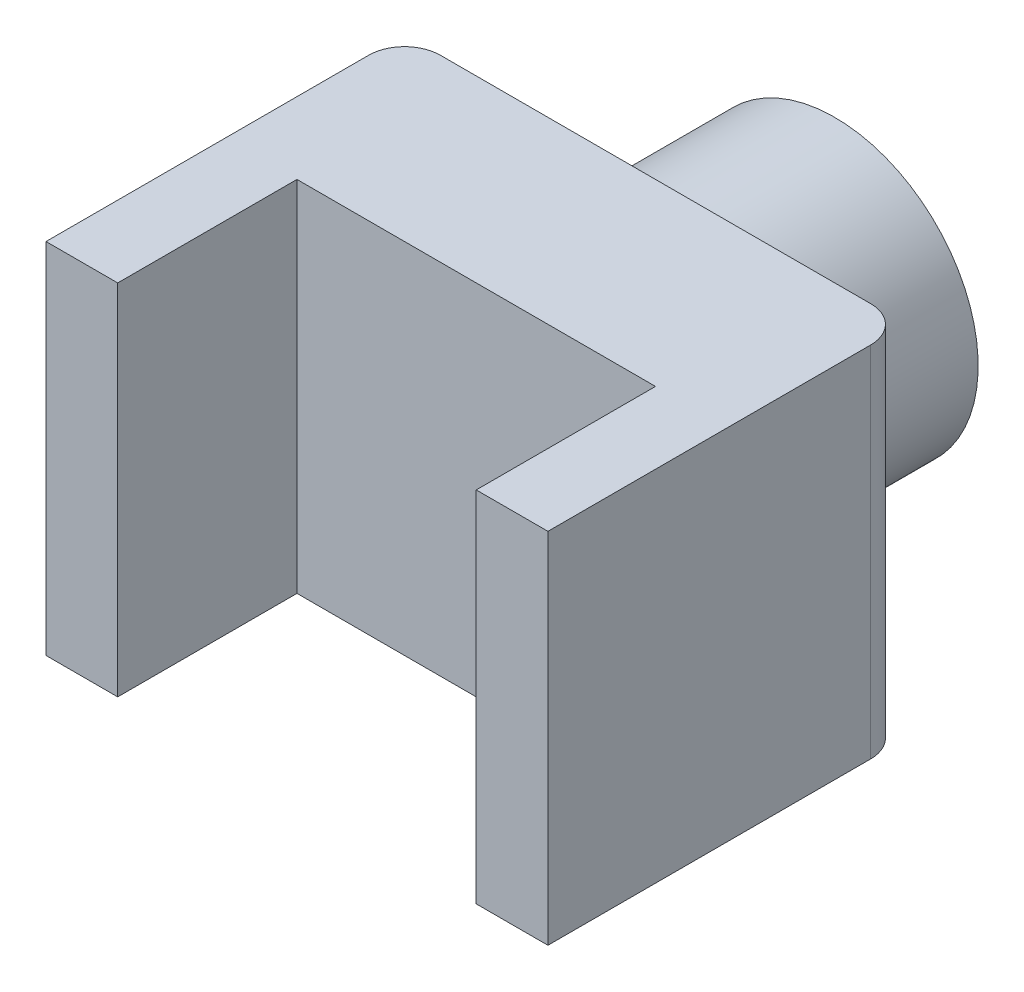
SolidWorks part; units mm, degrees
ref_plane "Plan de face" through (0, 0, 0) normal (0, 0, 1) x (1, 0, 0)
ref_plane "Plan de dessus" through (0, 0, 0) normal (0, 1, 0) x (1, 0, 0)
ref_plane "Plan de droite" through (0, 0, 0) normal (1, 0, 0) x (0, 0, -1)
sketch "Esquisse1" plane through (0, 0, 0) normal (0, 0, 1) x (1, 0, 0)
  line L1 (0, 0) -> (14, 0)
  line L2 (0, 0) -> (0, 10)
  line L3 (0, 10) -> (14, 10)
  line L4 (14, 0) -> (14, 10)
  dimension "D1" = 14
  dimension "D2" = 10
extrude "Boss.-Extru.1" add sketch "Esquisse1" along normal blind 10
sketch "Esquisse4" plane through (0, 0, 0) normal (0, 0, -1) x (-1, 0, 0)
  line L0 (-14, 10) -> (0, 10) construction
  line L1 (-14, 0) -> (-14, 10) construction
  circle A0 centre (-7, 5) radius 4
  dimension "D1" = 5
  dimension "D2" = 7
  dimension "D3" = 8
extrude "Boss.-Extru.2" add sketch "Esquisse4" along normal blind 5
sketch "Esquisse5" plane through (0, 0, -5) normal (0, 0, -1) x (-1, 0, 0)
  circle A0 centre (-7, 5) radius 2.5
  dimension "D1" = 5
extrude "Enlèv. mat.-Extru.2" cut sketch "Esquisse5" against normal blind 5
fillet "Congé3" radius 1 1 edges at (3, 5, 0)
fillet "Congé4" radius 1 2 edges at (0, 5, 0) (14, 5, 0)
sketch "Esquisse6" plane through (0, 0, 10) normal (0, 0, 1) x (1, 0, 0)
  line L0 (0, 0) -> (14, 0) construction
  line L1 (12, 0) -> (2, 0)
  line L2 (12, 0) -> (12, 10)
  line L3 (12, 10) -> (2, 10)
  line L4 (2, 0) -> (2, 10)
  line L5 (14, 10) -> (0, 10) construction
  line L6 (14, 0) -> (14, 10) construction
  line L7 (0, 10) -> (0, 0) construction
  dimension "D1" = 2
  dimension "D2" = 2
extrude "Enlèv. mat.-Extru.3" cut sketch "Esquisse6" against normal blind 5
